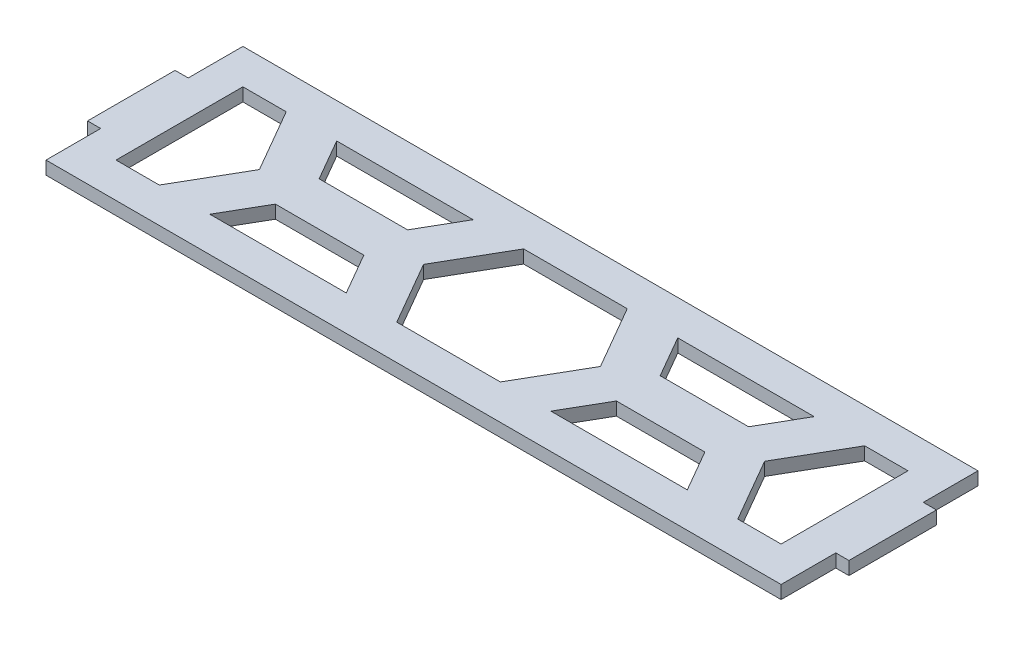
SolidWorks part; units mm, degrees
ref_plane "Front Plane" through (0, 0, 0) normal (0, 0, 1) x (1, 0, 0)
ref_plane "Top Plane" through (0, 0, 0) normal (0, 1, 0) x (1, 0, 0)
ref_plane "Right Plane" through (0, 0, 0) normal (1, 0, 0) x (0, 0, -1)
sketch "Sketch1" plane through (0, 0, 0) normal (0, 1, 0) x (1, 0, 0)
  line L0 (-87, 10) -> (-87, -10)
  line L1 (-87, -10) -> (-84, -10)
  line L2 (-84, -10) -> (-84, -22.5)
  line L3 (-84, -22.5) -> (84, -22.5)
  line L4 (84, -22.5) -> (84, -10)
  line L5 (84, -10) -> (87, -10)
  line L6 (87, -10) -> (87, 10)
  line L7 (87, 10) -> (84, 10)
  line L8 (84, 10) -> (84, 22.5)
  line L9 (84, 22.5) -> (-84, 22.5)
  line L10 (-84, 22.5) -> (-84, 10)
  line L11 (-84, 10) -> (-87, 10)
  point P13 (0, 22.5)
  point P17 (-87, 0)
  dimension "D1" = 168
  dimension "D2" = 3
  dimension "D3" = 20
  dimension "D4" = 45
extrude "Boss-Extrude1" add sketch "Sketch1" along normal mid plane 3
sketch "Sketch3" plane through (0, 0, 0) normal (0, 1, 0) x (1, 0, 0)
  line L0 (-106.8098, -5) -> (-127.0171, -5)
  line L1 (-106.8098, -50) -> (-127.0171, -50)
  line L2 (-127.0171, -50) -> (-137.1207, -67.5)
  line L3 (-137.1207, -67.5) -> (-127.0171, -85)
  line L4 (-127.0171, -85) -> (-106.8098, -85)
  line L5 (-106.8098, -85) -> (-96.7062, -67.5)
  line L6 (-96.7062, -67.5) -> (-106.8098, -50)
  line L13 (-127.0171, -5) -> (-137.1207, -22.5)
  line L14 (-98.1495, -90) -> (-88.0459, -107.5)
  line L15 (-88.0459, -107.5) -> (-67.8387, -107.5)
  line L16 (-67.8387, -107.5) -> (-57.735, -90)
  line L17 (-57.735, -90) -> (-67.8387, -72.5)
  line L18 (-67.8387, -72.5) -> (-88.0459, -72.5)
  line L19 (-88.0459, -72.5) -> (-98.1495, -90)
  line L20 (-137.1207, -22.5) -> (-127.0171, -40)
  line L21 (-127.0171, -40) -> (-106.8098, -40)
  line L22 (-106.8098, -40) -> (-96.7062, -22.5)
  line L23 (-96.7062, -22.5) -> (-106.8098, -5)
  line L24 (-98.1495, -45) -> (-88.0459, -62.5)
  line L25 (-88.0459, -62.5) -> (-67.8387, -62.5)
  line L26 (-67.8387, -62.5) -> (-57.735, -45)
  line L27 (-57.735, -45) -> (-67.8387, -27.5)
  line L28 (-67.8387, -27.5) -> (-88.0459, -27.5)
  line L29 (-88.0459, -27.5) -> (-98.1495, -45)
  line L30 (-106.8098, 40) -> (-127.0171, 40)
  line L31 (-127.0171, 40) -> (-137.1207, 22.5)
  line L32 (-137.1207, 22.5) -> (-127.0171, 5)
  line L33 (-127.0171, 5) -> (-106.8098, 5)
  line L34 (-106.8098, 5) -> (-96.7062, 22.5)
  line L35 (-96.7062, 22.5) -> (-106.8098, 40)
  line L36 (-98.1495, 0) -> (-88.0459, -17.5)
  line L37 (-88.0459, -17.5) -> (-67.8387, -17.5)
  line L38 (-67.8387, -17.5) -> (-57.735, 0)
  line L39 (-57.735, 0) -> (-67.8387, 17.5)
  line L40 (-67.8387, 17.5) -> (-88.0459, 17.5)
  line L41 (-88.0459, 17.5) -> (-98.1495, 0)
  line L42 (-106.8098, 85) -> (-127.0171, 85)
  line L43 (-127.0171, 85) -> (-137.1207, 67.5)
  line L44 (-137.1207, 67.5) -> (-127.0171, 50)
  line L45 (-127.0171, 50) -> (-106.8098, 50)
  line L46 (-106.8098, 50) -> (-96.7062, 67.5)
  line L47 (-96.7062, 67.5) -> (-106.8098, 85)
  line L48 (-98.1495, 45) -> (-88.0459, 27.5)
  line L49 (-88.0459, 27.5) -> (-67.8387, 27.5)
  line L50 (-67.8387, 27.5) -> (-57.735, 45)
  line L51 (-57.735, 45) -> (-67.8387, 62.5)
  line L52 (-67.8387, 62.5) -> (-88.0459, 62.5)
  line L53 (-88.0459, 62.5) -> (-98.1495, 45)
  line L54 (-106.8098, 130) -> (-127.0171, 130)
  line L55 (-127.0171, 130) -> (-137.1207, 112.5)
  line L56 (-137.1207, 112.5) -> (-127.0171, 95)
  line L57 (-127.0171, 95) -> (-106.8098, 95)
  line L58 (-106.8098, 95) -> (-96.7062, 112.5)
  line L59 (-96.7062, 112.5) -> (-106.8098, 130)
  line L60 (-98.1495, 90) -> (-88.0459, 72.5)
  line L61 (-88.0459, 72.5) -> (-67.8387, 72.5)
  line L62 (-67.8387, 72.5) -> (-57.735, 90)
  line L63 (-57.735, 90) -> (-67.8387, 107.5)
  line L64 (-67.8387, 107.5) -> (-88.0459, 107.5)
  line L65 (-88.0459, 107.5) -> (-98.1495, 90)
  line L66 (-106.8098, 175) -> (-127.0171, 175)
  line L67 (-127.0171, 175) -> (-137.1207, 157.5)
  line L68 (-137.1207, 157.5) -> (-127.0171, 140)
  line L69 (-127.0171, 140) -> (-106.8098, 140)
  line L70 (-106.8098, 140) -> (-96.7062, 157.5)
  line L71 (-96.7062, 157.5) -> (-106.8098, 175)
  line L72 (-98.1495, 135) -> (-88.0459, 117.5)
  line L73 (-88.0459, 117.5) -> (-67.8387, 117.5)
  line L74 (-67.8387, 117.5) -> (-57.735, 135)
  line L75 (-57.735, 135) -> (-67.8387, 152.5)
  line L76 (-67.8387, 152.5) -> (-88.0459, 152.5)
  line L77 (-88.0459, 152.5) -> (-98.1495, 135)
  line L102 (-106.8098, -50) -> (-106.8098, -5) construction
  line L103 (-88.0459, -72.5) -> (-88.0459, -62.5) construction
  line L104 (-101.758, -58.75) -> (-93.0977, -53.75) construction
  line L105 (-20.2073, 135) -> (-10.1036, 117.5)
  line L106 (-10.1036, 117.5) -> (10.1036, 117.5)
  line L107 (10.1036, 117.5) -> (20.2073, 135)
  line L108 (20.2073, 135) -> (10.1036, 152.5)
  line L109 (10.1036, 152.5) -> (-10.1036, 152.5)
  line L110 (-10.1036, 152.5) -> (-20.2073, 135)
  line L111 (-28.8675, 175) -> (-49.0748, 175)
  line L112 (-49.0748, 175) -> (-59.1784, 157.5)
  line L113 (-59.1784, 157.5) -> (-49.0748, 140)
  line L114 (-49.0748, 140) -> (-28.8675, 140)
  line L115 (-28.8675, 140) -> (-18.7639, 157.5)
  line L116 (-18.7639, 157.5) -> (-28.8675, 175)
  line L117 (-28.8675, 130) -> (-49.0748, 130)
  line L118 (-49.0748, 130) -> (-59.1784, 112.5)
  line L119 (-59.1784, 112.5) -> (-49.0748, 95)
  line L120 (-49.0748, 95) -> (-28.8675, 95)
  line L121 (-28.8675, 95) -> (-18.7639, 112.5)
  line L122 (-18.7639, 112.5) -> (-28.8675, 130)
  line L123 (-28.8675, 85) -> (-49.0748, 85)
  line L124 (-49.0748, 85) -> (-59.1784, 67.5)
  line L125 (-59.1784, 67.5) -> (-49.0748, 50)
  line L126 (-49.0748, 50) -> (-28.8675, 50)
  line L127 (-28.8675, 50) -> (-18.7639, 67.5)
  line L128 (-18.7639, 67.5) -> (-28.8675, 85)
  line L129 (-28.8675, 40) -> (-49.0748, 40)
  line L130 (-49.0748, 40) -> (-59.1784, 22.5)
  line L131 (-59.1784, 22.5) -> (-49.0748, 5)
  line L132 (-49.0748, 5) -> (-28.8675, 5)
  line L133 (-28.8675, 5) -> (-18.7639, 22.5)
  line L134 (-18.7639, 22.5) -> (-28.8675, 40)
  line L135 (-20.2073, 0) -> (-10.1036, -17.5)
  line L136 (-10.1036, -17.5) -> (10.1036, -17.5)
  line L137 (10.1036, -17.5) -> (20.2073, 0)
  line L138 (20.2073, 0) -> (10.1036, 17.5)
  line L139 (10.1036, 17.5) -> (-10.1036, 17.5)
  line L140 (-10.1036, 17.5) -> (-20.2073, 0)
  line L141 (-28.8675, -5) -> (-49.0748, -5)
  line L142 (-49.0748, -5) -> (-59.1784, -22.5)
  line L143 (-59.1784, -22.5) -> (-49.0748, -40)
  line L144 (-49.0748, -40) -> (-28.8675, -40)
  line L145 (-28.8675, -40) -> (-18.7639, -22.5)
  line L146 (-18.7639, -22.5) -> (-28.8675, -5)
  line L147 (-20.2073, -45) -> (-10.1036, -62.5)
  line L148 (-10.1036, -62.5) -> (10.1036, -62.5)
  line L149 (10.1036, -62.5) -> (20.2073, -45)
  line L150 (20.2073, -45) -> (10.1036, -27.5)
  line L151 (10.1036, -27.5) -> (-10.1036, -27.5)
  line L152 (-10.1036, -27.5) -> (-20.2073, -45)
  line L153 (-28.8675, -50) -> (-49.0748, -50)
  line L154 (-49.0748, -50) -> (-59.1784, -67.5)
  line L155 (-59.1784, -67.5) -> (-49.0748, -85)
  line L156 (-49.0748, -85) -> (-28.8675, -85)
  line L157 (-28.8675, -85) -> (-18.7639, -67.5)
  line L158 (-18.7639, -67.5) -> (-28.8675, -50)
  line L159 (-20.2073, -90) -> (-10.1036, -107.5)
  line L160 (-10.1036, -107.5) -> (10.1036, -107.5)
  line L161 (10.1036, -107.5) -> (20.2073, -90)
  line L162 (20.2073, -90) -> (10.1036, -72.5)
  line L163 (10.1036, -72.5) -> (-10.1036, -72.5)
  line L164 (-10.1036, -72.5) -> (-20.2073, -90)
  line L165 (-20.2073, 45) -> (-10.1036, 27.5)
  line L166 (-10.1036, 27.5) -> (10.1036, 27.5)
  line L167 (10.1036, 27.5) -> (20.2073, 45)
  line L168 (20.2073, 45) -> (10.1036, 62.5)
  line L169 (10.1036, 62.5) -> (-10.1036, 62.5)
  line L170 (-10.1036, 62.5) -> (-20.2073, 45)
  line L171 (-20.2073, 90) -> (-10.1036, 72.5)
  line L172 (-10.1036, 72.5) -> (10.1036, 72.5)
  line L173 (10.1036, 72.5) -> (20.2073, 90)
  line L174 (20.2073, 90) -> (10.1036, 107.5)
  line L175 (10.1036, 107.5) -> (-10.1036, 107.5)
  line L176 (-10.1036, 107.5) -> (-20.2073, 90)
  line L177 (57.735, 135) -> (67.8387, 117.5)
  line L178 (67.8387, 117.5) -> (88.0459, 117.5)
  line L179 (88.0459, 117.5) -> (98.1495, 135)
  line L180 (98.1495, 135) -> (88.0459, 152.5)
  line L181 (88.0459, 152.5) -> (67.8387, 152.5)
  line L182 (67.8387, 152.5) -> (57.735, 135)
  line L183 (49.0748, 175) -> (28.8675, 175)
  line L184 (28.8675, 175) -> (18.7639, 157.5)
  line L185 (18.7639, 157.5) -> (28.8675, 140)
  line L186 (28.8675, 140) -> (49.0748, 140)
  line L187 (49.0748, 140) -> (59.1784, 157.5)
  line L188 (59.1784, 157.5) -> (49.0748, 175)
  line L189 (49.0748, 130) -> (28.8675, 130)
  line L190 (28.8675, 130) -> (18.7639, 112.5)
  line L191 (18.7639, 112.5) -> (28.8675, 95)
  line L192 (28.8675, 95) -> (49.0748, 95)
  line L193 (49.0748, 95) -> (59.1784, 112.5)
  line L194 (59.1784, 112.5) -> (49.0748, 130)
  line L195 (49.0748, 85) -> (28.8675, 85)
  line L196 (28.8675, 85) -> (18.7639, 67.5)
  line L197 (18.7639, 67.5) -> (28.8675, 50)
  line L198 (28.8675, 50) -> (49.0748, 50)
  line L199 (49.0748, 50) -> (59.1784, 67.5)
  line L200 (59.1784, 67.5) -> (49.0748, 85)
  line L201 (49.0748, 40) -> (28.8675, 40)
  line L202 (28.8675, 40) -> (18.7639, 22.5)
  line L203 (18.7639, 22.5) -> (28.8675, 5)
  line L204 (28.8675, 5) -> (49.0748, 5)
  line L205 (49.0748, 5) -> (59.1784, 22.5)
  line L206 (59.1784, 22.5) -> (49.0748, 40)
  line L207 (57.735, 0) -> (67.8387, -17.5)
  line L208 (67.8387, -17.5) -> (88.0459, -17.5)
  line L209 (88.0459, -17.5) -> (98.1495, 0)
  line L210 (98.1495, 0) -> (88.0459, 17.5)
  line L211 (88.0459, 17.5) -> (67.8387, 17.5)
  line L212 (67.8387, 17.5) -> (57.735, 0)
  line L213 (49.0748, -5) -> (28.8675, -5)
  line L214 (28.8675, -5) -> (18.7639, -22.5)
  line L215 (18.7639, -22.5) -> (28.8675, -40)
  line L216 (28.8675, -40) -> (49.0748, -40)
  line L217 (49.0748, -40) -> (59.1784, -22.5)
  line L218 (59.1784, -22.5) -> (49.0748, -5)
  line L219 (57.735, -45) -> (67.8387, -62.5)
  line L220 (67.8387, -62.5) -> (88.0459, -62.5)
  line L221 (88.0459, -62.5) -> (98.1495, -45)
  line L222 (98.1495, -45) -> (88.0459, -27.5)
  line L223 (88.0459, -27.5) -> (67.8387, -27.5)
  line L224 (67.8387, -27.5) -> (57.735, -45)
  line L225 (49.0748, -50) -> (28.8675, -50)
  line L226 (28.8675, -50) -> (18.7639, -67.5)
  line L227 (18.7639, -67.5) -> (28.8675, -85)
  line L228 (28.8675, -85) -> (49.0748, -85)
  line L229 (49.0748, -85) -> (59.1784, -67.5)
  line L230 (59.1784, -67.5) -> (49.0748, -50)
  line L231 (57.735, -90) -> (67.8387, -107.5)
  line L232 (67.8387, -107.5) -> (88.0459, -107.5)
  line L233 (88.0459, -107.5) -> (98.1495, -90)
  line L234 (98.1495, -90) -> (88.0459, -72.5)
  line L235 (88.0459, -72.5) -> (67.8387, -72.5)
  line L236 (67.8387, -72.5) -> (57.735, -90)
  line L237 (57.735, 45) -> (67.8387, 27.5)
  line L238 (67.8387, 27.5) -> (88.0459, 27.5)
  line L239 (88.0459, 27.5) -> (98.1495, 45)
  line L240 (98.1495, 45) -> (88.0459, 62.5)
  line L241 (88.0459, 62.5) -> (67.8387, 62.5)
  line L242 (67.8387, 62.5) -> (57.735, 45)
  line L243 (57.735, 90) -> (67.8387, 72.5)
  line L244 (67.8387, 72.5) -> (88.0459, 72.5)
  line L245 (88.0459, 72.5) -> (98.1495, 90)
  line L246 (98.1495, 90) -> (88.0459, 107.5)
  line L247 (88.0459, 107.5) -> (67.8387, 107.5)
  line L248 (67.8387, 107.5) -> (57.735, 90)
  line L249 (135.6773, 135) -> (145.7809, 117.5)
  line L250 (145.7809, 117.5) -> (165.9882, 117.5)
  line L251 (165.9882, 117.5) -> (176.0918, 135)
  line L252 (176.0918, 135) -> (165.9882, 152.5)
  line L253 (165.9882, 152.5) -> (145.7809, 152.5)
  line L254 (145.7809, 152.5) -> (135.6773, 135)
  line L255 (127.0171, 175) -> (106.8098, 175)
  line L256 (106.8098, 175) -> (96.7062, 157.5)
  line L257 (96.7062, 157.5) -> (106.8098, 140)
  line L258 (106.8098, 140) -> (127.0171, 140)
  line L259 (127.0171, 140) -> (137.1207, 157.5)
  line L260 (137.1207, 157.5) -> (127.0171, 175)
  line L261 (127.0171, 130) -> (106.8098, 130)
  line L262 (106.8098, 130) -> (96.7062, 112.5)
  line L263 (96.7062, 112.5) -> (106.8098, 95)
  line L264 (106.8098, 95) -> (127.0171, 95)
  line L265 (127.0171, 95) -> (137.1207, 112.5)
  line L266 (137.1207, 112.5) -> (127.0171, 130)
  line L267 (127.0171, 85) -> (106.8098, 85)
  line L268 (106.8098, 85) -> (96.7062, 67.5)
  line L269 (96.7062, 67.5) -> (106.8098, 50)
  line L270 (106.8098, 50) -> (127.0171, 50)
  line L271 (127.0171, 50) -> (137.1207, 67.5)
  line L272 (137.1207, 67.5) -> (127.0171, 85)
  line L273 (127.0171, 40) -> (106.8098, 40)
  line L274 (106.8098, 40) -> (96.7062, 22.5)
  line L275 (96.7062, 22.5) -> (106.8098, 5)
  line L276 (106.8098, 5) -> (127.0171, 5)
  line L277 (127.0171, 5) -> (137.1207, 22.5)
  line L278 (137.1207, 22.5) -> (127.0171, 40)
  line L279 (135.6773, 0) -> (145.7809, -17.5)
  line L280 (145.7809, -17.5) -> (165.9882, -17.5)
  line L281 (165.9882, -17.5) -> (176.0918, 0)
  line L282 (176.0918, 0) -> (165.9882, 17.5)
  line L283 (165.9882, 17.5) -> (145.7809, 17.5)
  line L284 (145.7809, 17.5) -> (135.6773, 0)
  line L285 (127.0171, -5) -> (106.8098, -5)
  line L286 (106.8098, -5) -> (96.7062, -22.5)
  line L287 (96.7062, -22.5) -> (106.8098, -40)
  line L288 (106.8098, -40) -> (127.0171, -40)
  line L289 (127.0171, -40) -> (137.1207, -22.5)
  line L290 (137.1207, -22.5) -> (127.0171, -5)
  line L291 (135.6773, -45) -> (145.7809, -62.5)
  line L292 (145.7809, -62.5) -> (165.9882, -62.5)
  line L293 (165.9882, -62.5) -> (176.0918, -45)
  line L294 (176.0918, -45) -> (165.9882, -27.5)
  line L295 (165.9882, -27.5) -> (145.7809, -27.5)
  line L296 (145.7809, -27.5) -> (135.6773, -45)
  line L297 (127.0171, -50) -> (106.8098, -50)
  line L298 (106.8098, -50) -> (96.7062, -67.5)
  line L299 (96.7062, -67.5) -> (106.8098, -85)
  line L300 (106.8098, -85) -> (127.0171, -85)
  line L301 (127.0171, -85) -> (137.1207, -67.5)
  line L302 (137.1207, -67.5) -> (127.0171, -50)
  line L303 (135.6773, -90) -> (145.7809, -107.5)
  line L304 (145.7809, -107.5) -> (165.9882, -107.5)
  line L305 (165.9882, -107.5) -> (176.0918, -90)
  line L306 (176.0918, -90) -> (165.9882, -72.5)
  line L307 (165.9882, -72.5) -> (145.7809, -72.5)
  line L308 (145.7809, -72.5) -> (135.6773, -90)
  line L309 (135.6773, 45) -> (145.7809, 27.5)
  line L310 (145.7809, 27.5) -> (165.9882, 27.5)
  line L311 (165.9882, 27.5) -> (176.0918, 45)
  line L312 (176.0918, 45) -> (165.9882, 62.5)
  line L313 (165.9882, 62.5) -> (145.7809, 62.5)
  line L314 (145.7809, 62.5) -> (135.6773, 45)
  line L315 (135.6773, 90) -> (145.7809, 72.5)
  line L316 (145.7809, 72.5) -> (165.9882, 72.5)
  line L317 (165.9882, 72.5) -> (176.0918, 90)
  line L318 (176.0918, 90) -> (165.9882, 107.5)
  line L319 (165.9882, 107.5) -> (145.7809, 107.5)
  line L320 (145.7809, 107.5) -> (135.6773, 90)
  line L321 (-98.1495, 135) -> (-20.2073, 135) construction
  line L322 (-54.1266, -58.75) -> (-62.7868, -53.75) construction
  line L329 (-87, 10) -> (-87, -10) construction
  line L334 (84, 22.5) -> (-84, 22.5) construction
  line L335 (-76, -14.5) -> (76, -14.5)
  line L336 (-76, -14.5) -> (-76, 14.5)
  line L337 (-76, 14.5) -> (76, 14.5)
  line L338 (76, -14.5) -> (76, 14.5)
  line L339 (-76, -14.5) -> (76, 14.5) construction
  line L340 (-76, 14.5) -> (76, -14.5) construction
  line L341 (84, 10) -> (84, 22.5) construction
  circle A0 centre (-116.9134, -67.5) radius 17.5 construction
  circle A1 centre (-77.9423, -90) radius 17.5 construction
  point P10 (-88.0459, -67.5)
  point P303 (0, 0)
  point P306 (-87, 0)
  point P308 (0, 27.5)
  dimension "D3" = 35
  dimension "D2" = 45
  dimension "D5" = 8
  dimension "D6" = 8
  dimension "D1" = 6
  dimension "D4" = 4
extrude "Cut-Extrude1" cut sketch "Sketch3" against normal through all both and the other way through all contours L337 L336 L335 L38 L39 | L337 L140 L135 L335 L137 L138 | L335 L338 L337 L212 L207 | L214 L335 L218 L213 | L337 L203 L204 L205 | L142 L335 L146 L141 | L337 L131 L132 L133 region at (-68.753, 0, 0) region at (-38.9711, 0, 10.088) region at (-38.9711, 0, -10.088) region at (0, 0, 0) region at (38.9711, 0, 10.088) region at (38.9711, 0, -10.088) region at (68.753, 0, 0)
equation "\"bottomLength\"= 220mm"
equation "\"topLength\"= 330mm"
equation "\"frontHeight\"= 100mm"
equation "\"height\"= 180mm"
equation "\"width\"= 180mm"
equation "\"D1@Sketch1\"=\"width\"-12"
